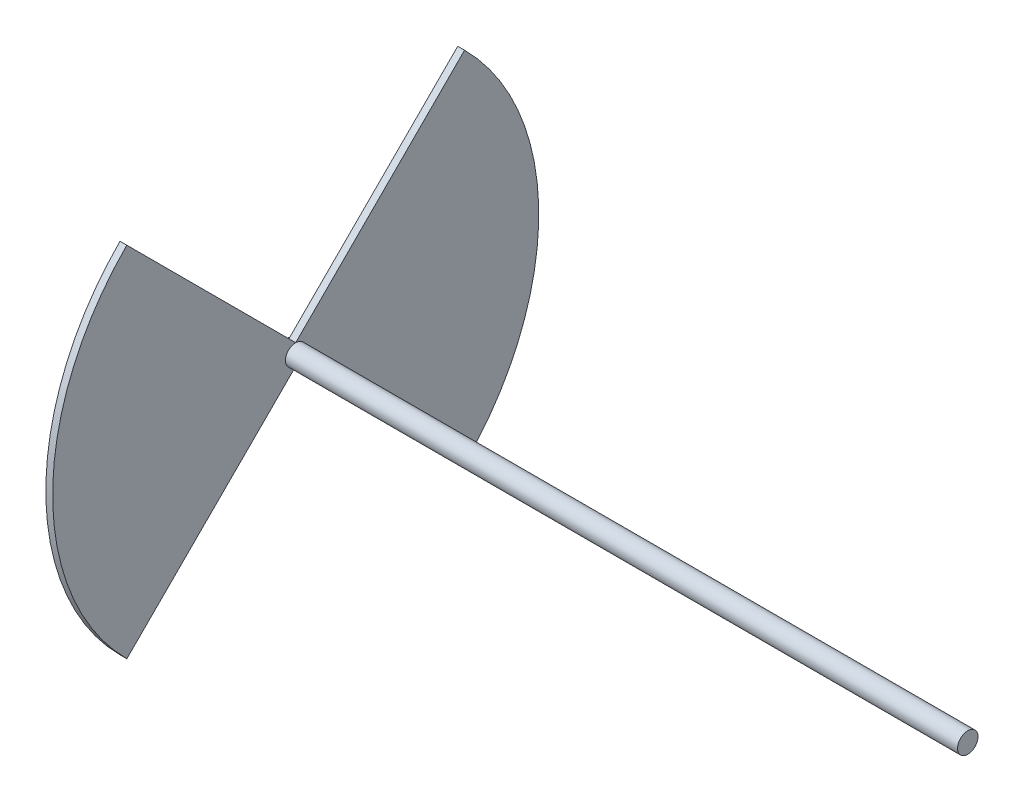
SolidWorks part; units mm, degrees
ref_plane "Plano frontal" through (0, 0, 0) normal (0, 0, 1) x (1, 0, 0)
ref_plane "Plano superior" through (0, 0, 0) normal (0, 1, 0) x (1, 0, 0)
ref_plane "Plano direito" through (0, 0, 0) normal (1, 0, 0) x (0, 0, -1)
sketch "Esboço1" plane through (0, 0, 0) normal (0, 0, 1) x (1, 0, 0)
  line L0 (0, 0) -> (0, 38.4066) construction
  line L1 (0, 0) -> (221.8378, 0) construction
  line L2 (0, 2.5) -> (3, 2.5)
  line L3 (3, 2.5) -> (3, 3)
  line L4 (3, 3) -> (200, 3)
  line L5 (200, 3) -> (200, 0)
  line L6 (200, 0) -> (0, 0)
  line L7 (0, 0) -> (0, 2.5)
  dimension "D1" = 5
  dimension "D2" = 6
  dimension "D3" = 3
  dimension "D4" = 200
revolve "Revolução1" add sketch "Esboço1" angle 360 about L1
sketch "Esboço2" plane through (3, 0, 0) normal (-1, 0, 0) x (0, 0, 1)
  line L0 (0, 3) -> (49.4975, 52.4975)
  line L1 (0, 0) -> (0, 16.0302) construction
  line L2 (0, 0) -> (37.3065, 0) construction
  line L3 (71.2426, 0) -> (71.2426, 14.5442) construction
  line L4 (0, -3) -> (49.4975, -52.4975)
  line L5 (0, -3) -> (-49.4975, -52.4975)
  line L6 (0, 3) -> (-49.4975, 52.4975)
  circle A2 centre (0, 0) radius 3 construction
  arc A3 (49.4975, 52.4975) -> (49.4975, -52.4975) centre (-3, 0) cw
  arc A4 (-49.4975, 52.4975) -> (-49.4975, -52.4975) centre (3, 0) ccw
  circle A5 centre (0, 0) radius 2.5
  circle A6 centre (0, 0) radius 2.5 construction
  dimension "D1" = 45
  dimension "D2" = 70
extrude "Ressalto-extrusão1" add sketch "Esboço2" along normal blind 2 separate body
